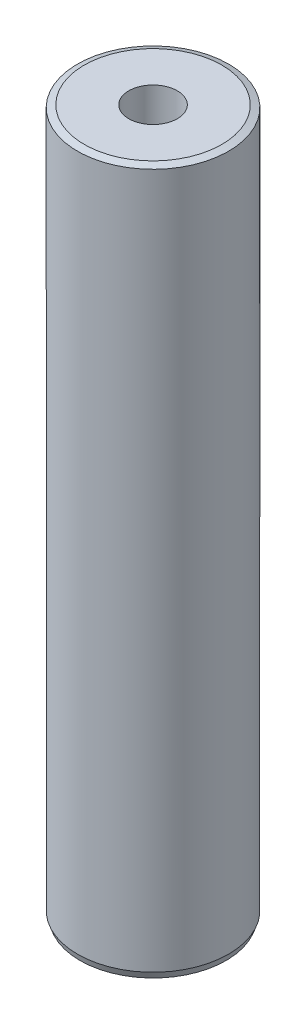
SolidWorks part; units mm, degrees
ref_plane "Front Plane" through (0, 0, 0) normal (0, 0, 1) x (1, 0, 0)
ref_plane "Top Plane" through (0, 0, 0) normal (0, 1, 0) x (1, 0, 0)
ref_plane "Right Plane" through (0, 0, 0) normal (1, 0, 0) x (0, 0, -1)
sketch "Sketch1" plane through (0, 0, 0) normal (0, 1, 0) x (1, 0, 0)
  circle A0 centre (0, 0) radius 47.5
  dimension "SHAFT_OD" = 95
extrude "Boss-Extrude1" add sketch "Sketch1" along normal blind 442.9755
sketch "Sketch2" plane through (0, 0, 0) normal (0, 1, 0) x (1, 0, 0)
  circle A0 centre (0, 0) radius 15.2539
  dimension "BORE_D" = 30.5079
extrude "Cut-Extrude1" cut sketch "Sketch2" along normal through all
chamfer "Chamfer1" distance 1.5621 angle 69.837 2 edges at (0, 442.9755, 47.5) (0, 0, 47.5) first distance on face at (0, 442.9755, 47.5) first distance on face at (0, 0, 15.2539)
